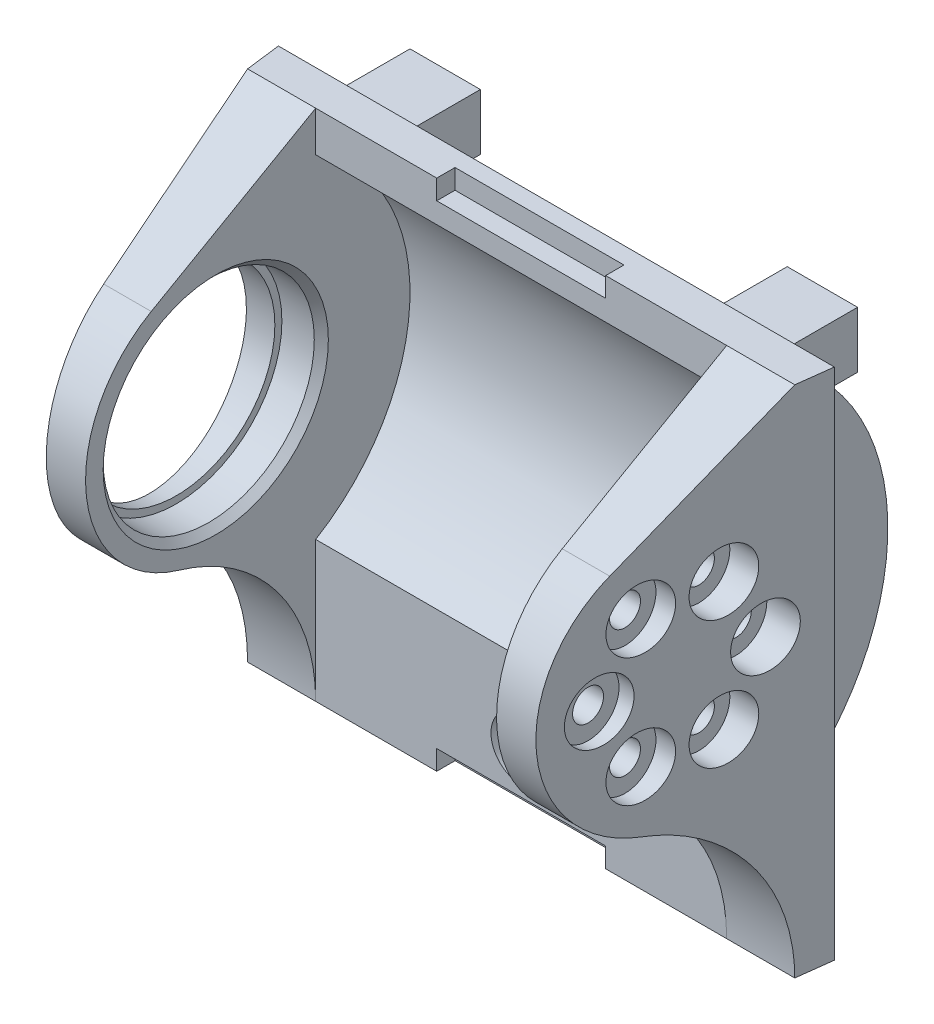
SolidWorks part; units mm, degrees
ref_plane "前视基准面" through (0, 0, 0) normal (0, 0, 1) x (1, 0, 0)
ref_plane "上视基准面" through (0, 0, 0) normal (0, 1, 0) x (1, 0, 0)
ref_plane "右视基准面" through (0, 0, 0) normal (1, 0, 0) x (0, 0, -1)
sketch "草图1" plane through (0, 0, 0) normal (0, 0, 1) x (1, 0, 0)
  line L1 (-19.75, 0) -> (19.75, 0)
  line L2 (-19.75, 0) -> (-19.75, 36.5)
  line L3 (-19.75, 36.5) -> (19.75, 36.5)
  line L4 (19.75, 0) -> (19.75, 36.5)
  dimension "D1" = 39.5
  dimension "D2" = 36.5
extrude "凸台-拉伸1" add sketch "草图1" along normal blind 2.5
sketch "草图2" plane through (-19.75, 0, 0) normal (-1, 0, 0) x (0, 0, 1)
  line L1 (0, 36.5) -> (0, 0) construction
  line L2 (2.5, 36.5) -> (2.5, 7.1276)
  line L3 (2.5, 36.5) -> (2.5, 0) construction
  line L4 (2.5, 7.1276) -> (2.5, 6.3858) construction
  arc A0 (2.5, 36.4724) -> (2.5, 7.1276) centre (9.6, 21.8) ccw
  arc A1 (2.5, 7.1276) -> (2.5, 36.4724) centre (9.6, 21.8) ccw construction
  line M4 (0, 36.5) -> (0, 0)
  line M6 (2.5, 0) -> (2.5, 36.5)
  dimension "D1" = 21.8
  dimension "D2" = 32.6
  dimension "D3" = 9.6
extrude "凸台-拉伸2" add sketch "草图2" against normal blind 34 from offset 2.6 contours A0 M6 M4 | A0 M4 region at (-19.75, 21.8, 1.2723) region at (-19.75, 21.8, -2.7336) offset against normal yes
sketch "草图3" plane through (0, 0, 0) normal (1, 0, 0) x (0, 0, -1)
  line L0 (-2.5, 36.5) -> (-14.1837, 29.8345)
  line L1 (-2.5, 36.5) -> (0, 36.5) construction
  line L2 (-2.5, 0) -> (-2.5, 36.5) construction
  line L5 (-2.5, 36.5) -> (-2.5, 0)
  arc A0 (-14.1837, 29.8345) -> (-12.2022, 12.9236) centre (-9.6, 21.8) ccw
  arc A1 (-2.5, 0) -> (-12.2022, 12.9236) centre (-16, -0.0312) ccw
  arc A2 (-12.2022, 12.9236) -> (-2.5, 0) centre (-16, -0.0312) ccw construction
  arc A3 (-2.5, 27.729) -> (-14.1837, 29.8345) centre (-9.6, 21.8) ccw construction
  arc A4 (-12.2022, 12.9236) -> (-2.5, 15.871) centre (-9.6, 21.8) ccw construction
  arc A5 (-2.5, 15.871) -> (-2.5, 27.729) centre (-9.6, 21.8) ccw construction
  dimension "D1" = 9.6
  dimension "D2" = 21.8
  dimension "D3" = 18.5
  dimension "D4" = 27
extrude "凸台-拉伸3" add sketch "草图3" along normal through all from offset 14.6
ref_axis "基准轴1" through (19.75, 21.8, 9.6) along (-1, 0, 0)
mirror "镜向1" about plane through (0, 0, 0) normal (1, 0, 0) of "凸台-拉伸3"
sketch "草图4" plane through (0, 0, 0) normal (0, 0, -1) x (-1, 0, 0)
  line L0 (0, 36.5) -> (0, 0) construction
  line L1 (-15.9, 35.5) -> (-10.9, 35.5)
  line L2 (-15.9, 35.5) -> (-15.9, 31.5)
  line L3 (-15.9, 31.5) -> (-10.9, 31.5)
  line L4 (-10.9, 35.5) -> (-10.9, 31.5)
  line L5 (-19.75, 36.5) -> (19.75, 36.5) construction
  line L6 (19.75, 0) -> (-19.75, 0) construction
  line L7 (10.9, 35.5) -> (10.9, 31.5)
  line L8 (15.9, 31.5) -> (10.9, 31.5)
  line L9 (15.9, 35.5) -> (15.9, 31.5)
  line L10 (15.9, 35.5) -> (10.9, 35.5)
  dimension "D1" = 10.9
  dimension "D2" = 5
  dimension "D3" = 4
  dimension "D4" = 1
extrude "凸台-拉伸4" add sketch "草图4" along normal blind 5.5
sketch "草图5" plane through (0, 0, -5.5) normal (0, 0, -1) x (-1, 0, 0)
  line L14 (-14.4, 34) -> (-14.4, 33)
  line L15 (-14.4, 33) -> (-12.4, 33)
  line L16 (-12.4, 33) -> (-12.4, 34)
  line L17 (-12.4, 34) -> (-14.4, 34)
  line L18 (-14.4, 34) -> (-14.4, 33)
  line L19 (-14.4, 33) -> (-12.4, 33)
  line L20 (-12.4, 33) -> (-12.4, 34)
  line L21 (-12.4, 34) -> (-14.4, 34)
  line L26 (14.4, 34) -> (12.4, 34)
  line L27 (12.4, 34) -> (12.4, 33)
  line L28 (12.4, 33) -> (14.4, 33)
  line L29 (14.4, 33) -> (14.4, 34)
  line L30 (14.4, 34) -> (12.4, 34)
  line L31 (12.4, 34) -> (12.4, 33)
  line L32 (12.4, 33) -> (14.4, 33)
  line L33 (14.4, 33) -> (14.4, 34)
  dimension "D1" = 1.5
  dimension "D2" = 1.5
extrude "切除-拉伸1" cut sketch "草图5" against normal up to surface (3.2573 mm away) up to face at (-0.05, 29.4687, -2.3272)
sketch "草图6" plane through (-14.6, 0, 0) normal (1, 0, 0) x (0, 0, -1)
  line L0 (0, 31.7136) -> (0, 11.8864)
  line L1 (0, 8.6269) -> (0, 34.9731) construction
  arc A0 (0, 11.8864) -> (0, 31.7136) centre (-9.6, 21.8) ccw construction
  arc A1 (-14.1837, 29.8345) -> (-12.2022, 12.9236) centre (-9.6, 21.8) ccw construction
  arc A2 (0, 31.7136) -> (0, 11.8864) centre (-9.6, 21.8) ccw
  dimension "D1" = 27.6
  dimension "D2" = 9.6
extrude "切除-拉伸2" cut sketch "草图6" along normal up to surface (29.2 mm away) up to face at (14.6, 20.0536, 8.7082)
sketch "草图7" plane through (-14.6, 0, 0) normal (1, 0, 0) x (0, 0, -1)
  circle A0 centre (-9.6, 21.8) radius 7.5
  arc A1 (-14.1837, 29.8345) -> (-12.2022, 12.9236) centre (-9.6, 21.8) ccw construction
  dimension "D1" = 15
extrude "切除-拉伸3" cut sketch "草图7" against normal blind 2.8
sketch "草图8" plane through (-17.4, 0, 0) normal (1, 0, 0) x (0, 0, -1)
  circle A0 centre (-9.6, 21.8) radius 7
  circle A1 centre (-9.6, 21.8) radius 7.5 construction
  dimension "D1" = 14
extrude "切除-拉伸4" cut sketch "草图8" against normal through all
chamfer "倒角1" distance 0.5 angle 45 1 edges at (-14.6, 21.8, 2.1)
sketch "草图9" plane through (0, 0, 2.5) normal (0, 0, 1) x (1, 0, 0)
  line L0 (14.6, 36.5) -> (-14.6, 36.5) construction
  line L1 (-6, 36.5) -> (6, 36.5)
  line L2 (-6, 36.5) -> (-6, 35.1)
  line L3 (-6, 35.1) -> (6, 35.1)
  line L4 (6, 36.5) -> (6, 35.1)
  line L5 (0, 36.5) -> (0, 0) construction
  line L6 (-14.6, 0) -> (14.6, 0) construction
  point P12 (0, 0)
  dimension "D1" = 1.4
  dimension "D2" = 12
extrude "切除-拉伸5" cut sketch "草图9" against normal blind 1.3
hole_wizard "M2 六角圆柱头螺钉的柱形沉头孔1" positions "草图11" profile "草图12" counterbore size "M2" standard "GB" end condition through all
sketch "草图11" plane through (0, 0, 2.5) normal (0, 0, 1) x (1, 0, 0)
  line L0 (-14.6, 0) -> (14.6, 0) construction
  point P0 (0, 4.3)
  dimension "D1" = 4.3
sketch "草图12" plane through (0, 4.3, 2.5) normal (1, 0, 0) x (0, -1, 0)
  line L0 (0, 0) -> (0, 9.2)
  line L1 (0, 9.2) -> (1.1, 9.2)
  line L3 (1.1, 9.2) -> (1.1, 1)
  line L4 (1.1, 1) -> (2.15, 1)
  line L5 (2.15, 1) -> (2.15, 0)
  line L7 (2.15, 0) -> (0, 0)
  line L11 (0, -6.35) -> (0, 107.95) construction
  dimension "通孔孔直径" = 2.2
  dimension "通孔孔深度" = 9.2
  dimension "柱形沉头孔直径" = 4.3
  dimension "柱形沉头孔深度" = 1
sketch "草图10" plane through (0, 0, 2.5) normal (0, 0, 1) x (1, 0, 0)
  line L0 (-14.6, 0) -> (14.6, 0) construction
  line L1 (-6, 1.4) -> (6, 1.4)
  line L2 (-6, 1.4) -> (-6, 0)
  line L3 (-6, 0) -> (6, 0)
  line L4 (6, 1.4) -> (6, 0)
  point P8 (0, 0)
  dimension "D1" = 1.4
  dimension "D2" = 12
extrude "切除-拉伸6" cut sketch "草图10" against normal blind 1.3
hole_wizard "M2 六角圆柱头螺钉的柱形沉头孔2" positions "草图13" profile "草图15" counterbore size "M2" standard "GB"
sketch "草图13" plane through (19.75, 0, 0) normal (1, 0, 0) x (0, 0, -1)
  line L0 (-14.85, 21.8) -> (-9.6, 21.8)
  arc A0 (-14.1837, 29.8345) -> (-12.2022, 12.9236) centre (-9.6, 21.8) ccw construction
  point P3 (-14.85, 21.8)
  dimension "D1" = 5.25
sketch "草图15" plane through (19.75, 21.8, 14.85) normal (0, 1, 0) x (0, 0, -1)
  line L0 (0, 0) -> (0, 7.8609)
  line L1 (0, 7.8609) -> (1.1, 7.2)
  line L2 (1.1, 7.2) -> (1.1, 2.65)
  line L3 (1.1, 2.65) -> (2.2, 2.65)
  line L4 (2.2, 2.65) -> (2.2, 0)
  line L5 (2.2, 0) -> (0, 0)
  line L10 (0, 7.8609) -> (-1.1, 7.2) construction
  line L11 (0, -6.35) -> (0, 107.95) construction
  dimension "孔直径" = 2.2
  dimension "孔深度" = 7.2
  dimension "柱形沉头孔直径" = 4.4
  dimension "柱形沉头孔深度" = 2.65
  dimension "导头角度" = 118
pattern_circular "阵列(圆周)1" count 6 over 360 about axis through (19.75, 21.8, 9.6) along (-1, 0, 0) of "M2 六角圆柱头螺钉的柱形沉头孔2"
sketch "草图16" plane through (0, 36.5, 0) normal (0, 1, 0) x (1, 0, 0)
  line L0 (19.75, 0) -> (17.3921, -18.85)
  line L1 (19.75, 0) -> (19.75, -18.85)
  line L2 (14.6, -18.85) -> (19.75, -18.85) construction
  line L3 (17.3921, -18.85) -> (19.75, -18.85)
  line L4 (0, 0) -> (0, -18.3075) construction
  line L5 (19.75, 0) -> (-19.75, 0) construction
  line L6 (-17.3921, -18.85) -> (-19.75, -18.85)
  line L7 (-19.75, 0) -> (-19.75, -18.85)
  line L8 (-19.75, 0) -> (-17.3921, -18.85)
  dimension "D1" = 7.13
extrude "切除-拉伸7" cut sketch "草图16" against normal through all
sketch "草图17" plane through (-14.6, 0, 0) normal (1, 0, 0) x (0, 0, -1)
  arc A0 (0, 8.6269) -> (0, 34.9731) centre (-9.6, 21.8) ccw construction
  arc A1 (0, 8.6269) -> (0, 34.9731) centre (-9.6, 21.8) ccw construction
  circle A2 centre (-9.6, 21.8) radius 13.8
extrude "切除-拉伸8" cut sketch "草图17" along normal up to surface (29.2 mm away) up to face at (14.6, 17.2534, 11.125)
